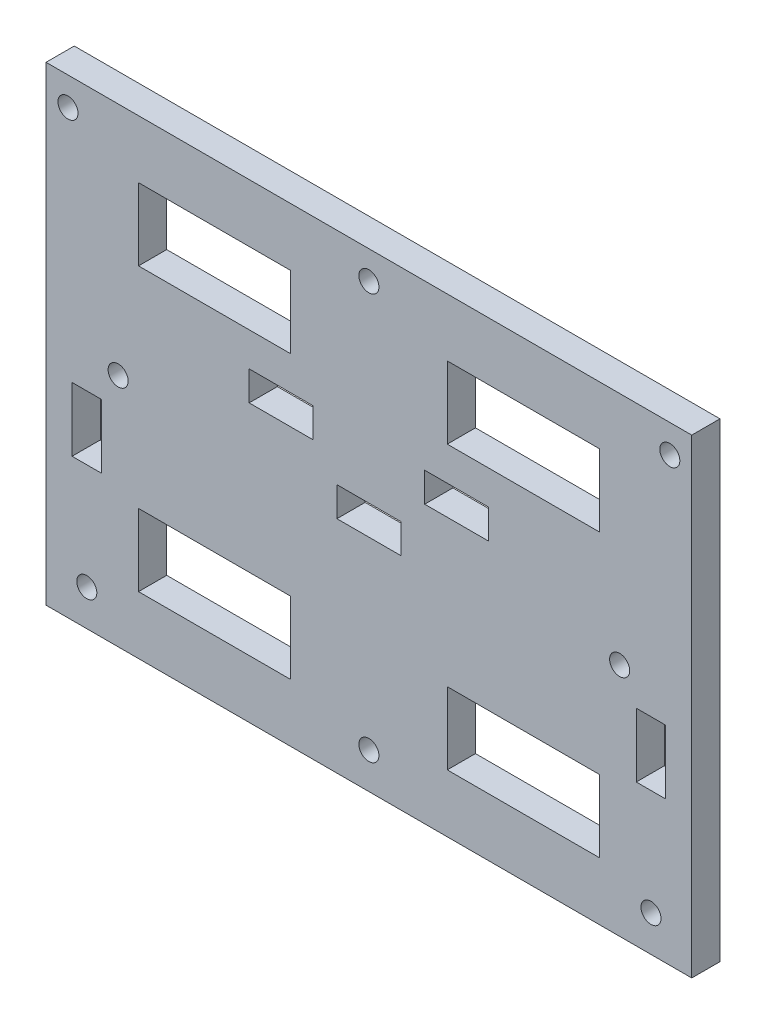
SolidWorks part; units mm, degrees
ref_plane "Front Plane" through (0, 0, 0) normal (0, 0, 1) x (1, 0, 0)
ref_plane "Top Plane" through (0, 0, 0) normal (0, 1, 0) x (1, 0, 0)
ref_plane "Right Plane" through (0, 0, 0) normal (1, 0, 0) x (0, 0, -1)
sketch "Sketch1" plane through (0, 0, 0) normal (0, 0, 1) x (1, 0, 0)
  line L0 (0, -37.5) -> (0, 37.5) construction
  line L1 (-51.5, -37.5) -> (51.5, -37.5)
  line L2 (-51.5, -37.5) -> (-51.5, 37.5)
  line L3 (-51.5, 37.5) -> (51.5, 37.5)
  line L4 (51.5, -37.5) -> (51.5, 37.5)
  line L5 (-51.5, -37.5) -> (51.5, 37.5) construction
  line L6 (-51.5, 37.5) -> (51.5, -37.5) construction
  line L7 (-51.5, 0) -> (51.5, 0) construction
  line L8 (-51.5, 22.5) -> (51.5, 22.5) construction
  line L9 (36.75, 16.75) -> (12.5, 28.25) construction
  line L10 (-36.75, 28.25) -> (-12.5, 28.25)
  line L11 (-36.75, 28.25) -> (-36.75, 16.75)
  line L12 (-36.75, 16.75) -> (-12.5, 16.75)
  line L13 (-12.5, 28.25) -> (-12.5, 16.75)
  line L14 (-36.75, 28.25) -> (-12.5, 16.75) construction
  line L15 (-36.75, 16.75) -> (-12.5, 28.25) construction
  line L16 (36.75, 28.25) -> (12.5, 16.75) construction
  line L17 (12.5, 28.25) -> (12.5, 16.75)
  line L18 (36.75, 16.75) -> (12.5, 16.75)
  line L19 (36.75, 28.25) -> (36.75, 16.75)
  line L20 (36.75, 28.25) -> (12.5, 28.25)
  line L21 (36.75, -28.25) -> (12.5, -16.75) construction
  line L22 (-36.75, -16.75) -> (-12.5, -28.25) construction
  line L23 (-36.75, -28.25) -> (-12.5, -16.75) construction
  line L24 (36.75, -16.75) -> (12.5, -28.25) construction
  line L25 (36.75, -28.25) -> (12.5, -28.25)
  line L26 (36.75, -28.25) -> (36.75, -16.75)
  line L27 (36.75, -16.75) -> (12.5, -16.75)
  line L28 (12.5, -28.25) -> (12.5, -16.75)
  line L29 (-12.5, -28.25) -> (-12.5, -16.75)
  line L30 (-36.75, -16.75) -> (-12.5, -16.75)
  line L31 (-36.75, -28.25) -> (-36.75, -16.75)
  line L32 (-36.75, -28.25) -> (-12.5, -28.25)
  point P0 (0, 0)
  point P12 (-24.625, 22.5)
  point P21 (24.625, 22.5)
  point P30 (24.625, -22.5)
  point P31 (-24.625, -22.5)
  dimension "D1" = 103
  dimension "D2" = 75
  dimension "D3" = 22.5
  dimension "D4" = 24.25
  dimension "D5" = 11.5
  dimension "D6" = 12.5
extrude "Boss-Extrude1" add sketch "Sketch1" along normal blind 4.5
sketch "Sketch2" plane through (0, 0, 4.5) normal (0, 0, 1) x (1, 0, 0)
  line L0 (0, -37.5) -> (0, 37.5) construction
  line L1 (-51.5, -37.5) -> (51.5, -37.5) construction
  line L2 (51.5, 37.5) -> (-51.5, 37.5) construction
  line L3 (-51.5, 0) -> (51.5, 0) construction
  line L4 (-51.5, 37.5) -> (-51.5, -37.5) construction
  line L5 (51.5, -37.5) -> (51.5, 37.5) construction
  line L6 (-40, 0) -> (40, 0) construction
  line L7 (-48, 33) -> (48, 33) construction
  circle A0 centre (-48, 33) radius 1.6
  circle A1 centre (48, 33) radius 1.6
  circle A2 centre (40, 0) radius 1.6
  circle A3 centre (-40, 0) radius 1.6
  circle A4 centre (0, 33) radius 1.6
  dimension "D1" = 3.2
  dimension "D7" = 3.2
  dimension "D8" = 3.2
  dimension "D9" = 3.2
  dimension "D2" = 48
  dimension "D3" = 33
  dimension "D4" = 80
  dimension "D5" = 40
  dimension "D6" = 0
extrude "screwHoles" cut sketch "Sketch2" against normal through all
sketch "Sketch3" plane through (0, 0, 4.5) normal (0, 0, 1) x (1, 0, 0)
  line L0 (-51.5, 9) -> (26.0486, 9) construction
  line L1 (-51.5, 37.5) -> (-51.5, -37.5) construction
  line L3 (0, 37.5) -> (0, -37.5) construction
  line L4 (51.5, 37.5) -> (-51.5, 37.5) construction
  line L5 (-51.5, -37.5) -> (51.5, -37.5) construction
  line L6 (19.1, 6.65) -> (8.9, 11.35) construction
  line L7 (-19.1, 11.35) -> (-8.9, 11.35)
  line L8 (-19.1, 11.35) -> (-19.1, 6.65)
  line L9 (-19.1, 6.65) -> (-8.9, 6.65)
  line L10 (-8.9, 11.35) -> (-8.9, 6.65)
  line L11 (-19.1, 11.35) -> (-8.9, 6.65) construction
  line L12 (-19.1, 6.65) -> (-8.9, 11.35) construction
  line L13 (19.1, 11.35) -> (8.9, 6.65) construction
  line L14 (8.9, 11.35) -> (8.9, 6.65)
  line L15 (19.1, 6.65) -> (8.9, 6.65)
  line L16 (19.1, 11.35) -> (19.1, 6.65)
  line L17 (19.1, 11.35) -> (8.9, 11.35)
  line L18 (-51.5, 37.5) -> (-51.5, -37.5) construction
  point P2 (-51.5, 0)
  point P12 (-14, 9)
  point P21 (14, 9)
  dimension "D1" = 10.2
  dimension "D2" = 4.7
  dimension "D3" = 14
  dimension "D4" = 9
extrude "BeltClamp" cut sketch "Sketch3" against normal through all
sketch "Sketch4" plane through (0, 0, 4.5) normal (0, 0, 1) x (1, 0, 0)
  line L0 (-51.5, 0) -> (51.5, 0) construction
  line L1 (-51.5, 37.5) -> (-51.5, -37.5) construction
  line L2 (51.5, -37.5) -> (51.5, 37.5) construction
  line L4 (-5.1, 2.35) -> (5.1, 2.35)
  line L5 (-5.1, 2.35) -> (-5.1, -2.35)
  line L6 (-5.1, -2.35) -> (5.1, -2.35)
  line L7 (5.1, 2.35) -> (5.1, -2.35)
  line L8 (-5.1, 2.35) -> (5.1, -2.35) construction
  line L9 (-5.1, -2.35) -> (5.1, 2.35) construction
  circle A0 centre (-40, 0) radius 1.6 construction
  point P6 (0, 0)
  dimension "D1" = 10.2
  dimension "D2" = 4.7
  dimension "D3" = 0
extrude "Cut-Extrude3" cut sketch "Sketch4" against normal through all
sketch "Sketch5" plane through (0, 0, 4.5) normal (0, 0, 1) x (1, 0, 0)
  line L0 (-51.5, -9.75) -> (51.5, -9.75) construction
  line L1 (-51.5, 37.5) -> (-51.5, -37.5) construction
  line L2 (51.5, -37.5) -> (51.5, 37.5) construction
  line L3 (5.1, -2.35) -> (5.1, 2.35) construction
  line L4 (0, -37.5) -> (0, 37.5) construction
  line L5 (-51.5, -37.5) -> (51.5, -37.5) construction
  line L6 (51.5, 37.5) -> (-51.5, 37.5) construction
  line L7 (-42.65, -14.85) -> (-47.35, -4.65) construction
  line L8 (42.65, -4.65) -> (47.35, -4.65)
  line L9 (42.65, -4.65) -> (42.65, -14.85)
  line L10 (42.65, -14.85) -> (47.35, -14.85)
  line L11 (47.35, -4.65) -> (47.35, -14.85)
  line L12 (42.65, -4.65) -> (47.35, -14.85) construction
  line L13 (42.65, -14.85) -> (47.35, -4.65) construction
  line L14 (-42.65, -4.65) -> (-47.35, -14.85) construction
  line L15 (-47.35, -4.65) -> (-47.35, -14.85)
  line L16 (-42.65, -14.85) -> (-47.35, -14.85)
  line L17 (-42.65, -4.65) -> (-42.65, -14.85)
  line L18 (-42.65, -4.65) -> (-47.35, -4.65)
  line L19 (45, -9.75) -> (45, -37.5) construction
  line L20 (-45, -9.75) -> (-45, -37.5) construction
  line L21 (-45, -31.75) -> (45, -31.75) construction
  circle A0 centre (45, -31.75) radius 1.6
  circle A1 centre (-45, -31.75) radius 1.6
  circle A2 centre (0, -31.75) radius 1.6
  point P6 (5.1, 0)
  point P15 (45, -9.75)
  point P24 (-45, -9.75)
  dimension "D5" = 3.2
  dimension "D7" = 3.2
  dimension "D1" = 9.75
  dimension "D2" = 10.2
  dimension "D3" = 4.7
  dimension "D4" = 45
  dimension "D6" = 22
extrude "Cut-Extrude4" cut sketch "Sketch5" against normal through all
sketch "Sketch6" plane through (0, 0, 4.5) normal (0, 0, 1) x (1, 0, 0)
  line L0 (-47.35, -9.75) -> (47.35, -9.75) construction
  line L1 (-47.35, -4.65) -> (-47.35, -14.85) construction
  line L2 (47.35, -14.85) -> (47.35, -4.65) construction
  line L3 (0, -2.35) -> (0, -37.5) construction
  line L4 (-5.1, -2.35) -> (5.1, -2.35) construction
  line L5 (-51.5, -37.5) -> (51.5, -37.5) construction
  line L6 (45, -14.85) -> (45, -4.65) construction
  line L7 (42.65, -14.85) -> (47.35, -14.85) construction
  line L8 (47.35, -4.65) -> (42.65, -4.65) construction
  line L9 (42.65, -4.65) -> (42.65, -14.85) construction
  line L10 (41.65, -15.85) -> (48.35, -15.85)
  line L11 (41.65, -15.85) -> (41.65, -3.65)
  line L12 (41.65, -3.65) -> (48.35, -3.65)
  line L13 (48.35, -15.85) -> (48.35, -3.65)
  line L14 (41.65, -15.85) -> (48.35, -3.65) construction
  line L15 (41.65, -3.65) -> (48.35, -15.85) construction
  line L16 (-41.65, -3.65) -> (-48.35, -15.85) construction
  line L17 (-41.65, -15.85) -> (-48.35, -3.65) construction
  line L18 (-45, -14.85) -> (-45, -4.65) construction
  line L19 (-48.35, -15.85) -> (-48.35, -3.65)
  line L20 (-41.65, -3.65) -> (-48.35, -3.65)
  line L21 (-41.65, -15.85) -> (-41.65, -3.65)
  line L22 (-41.65, -15.85) -> (-48.35, -15.85)
  circle A0 centre (45, -9.75) radius 1.6
  circle A1 centre (-45, -9.75) radius 1.6
  point P18 (45, -9.75)
  dimension "D3" = 3.2
  dimension "D1" = 1
  dimension "D2" = 1
extrude "FrontToRear1" [suppressed] add sketch "Sketch6" against normal up to surface (4.5 mm away) up to face at (1.6, -31.75, 0)
sketch "Sketch7" plane through (0, 0, 4.5) normal (0, 0, 1) x (1, 0, 0)
  line L0 (5.1, 2.35) -> (-5.1, 2.35) construction
  line L1 (-45, -3.35) -> (45, -3.35)
  line L2 (-45, -3.35) -> (-45, 3.35)
  line L3 (-45, 3.35) -> (45, 3.35)
  line L4 (45, -3.35) -> (45, 3.35)
  line L5 (-45, -3.35) -> (45, 3.35) construction
  line L6 (-45, 3.35) -> (45, -3.35) construction
  circle A0 centre (40, 0) radius 1.6 construction
  point P0 (0, 0)
  dimension "D1" = 1
  dimension "D2" = 5
extrude "FrontToRear2" [suppressed] add sketch "Sketch7" against normal through all
equation "\"X-ROD-SPACING\"=45"
equation "\"Y-ROD-SPACING\"=75"
equation "\"Z-ROD-SPACING\"=17.5"
equation "\"Y-BED-OFFSET\"=2"
equation "\"Y-BED-ROD-INSET\"=3.5"
equation "\"Y-BED-SCREW-SPACING\"=209"
equation "\"Y-BED-SCREW-CUTOUT-SLOT-HEIGHT\"=1"
equation "\"T-SLOT-NUT-FILLET-RADIUS\"=0.25"
equation "\"T-SLOT-SCREW-SHAFT-RADIUS\"=1.75"
equation "\"T-SLOT-SCREW-SHAFT-CUTOUT-LENGTH\"=10.5"
equation "\"T-SLOT-NUT-DEPTH\"=4.2"
equation "\"T-SLOT-NUT-WIDTH\"=3"
equation "\"T-SLOT-NUT-END-DISTANCE\"=8"
equation "\"ACRYLIC-THICKNESS\"=10"
equation "\"ACRYLIC-THICKNESS2\"=4.5"
equation "\"ACRYLIC-TAB-CUTOUT-SIZE\"=\"ACRYLIC-THICKNESS\"+\"ACRYLIC-TAB-TOLERANCE\"*2"
equation "\"ACRYLIC-TAB-WIDTH\"=\"ACRYLIC-THICKNESS\""
equation "\"ACRYLIC-M3-HOLE\"=3.2"
equation "\"SMOOTHROD-CAP-SCREW-DISTANCE\"=20"
equation "\"FRAME-WIDTH-INNER\"=370"
equation "\"NEMA17-HOLE-SPACING\"=31"
equation "\"NEMA17-CENTRAL-CUTOUT\"=22.5"
equation "\"Z-BRACKET-REACH\"=55"
equation "\"Z-ROD-INSET\"=16"
equation "\"TOP-BRACKET-SPACING\"=40"
equation "\"SMOOTHROD-X-LENGTH\"=350"
equation "\"SMOOTHROD-Y-LENGTH\"=350"
equation "\"SMOOTHROD-Z-LENGTH\"=350"
equation "\"SMOOTHROD-TIGHTENING-HEADROOM\"=1"
equation "\"LEADSCREW-Z-LENGTH\"=300"
equation "\"SCREW-LENGTH-FRAME\"=\"ACRYLIC-THICKNESS\" + 10"
equation "\"SCREW-LENGTH-MOTOR\"=\"ACRYLIC-THICKNESS\" + 5"
equation "\"SCREW-HEAD-RADIUS\"=6"
equation "\"PRINTED-X-SMOOTHROD-DIAMETER\"=8.2"
equation "\"PRINTED-X-SMOOTHROD-CUTOUT\"=10"
equation "\"PRINTED-X-BASE-HEIGHT\"=10"
equation "\"PRINTED-LM8UU-CUTOUT-SIZE\"=15.25"
equation "\"PRINTED-LM8UU-CUTOUT-LENGTH\"=24.5"
equation "\"PRINTED-X-IDLER-HEIGHT\"=16"
equation "\"PSU-MOUNTING-WIDTH\"=95"
equation "\"PSU-MOUNTING-HEIGHT\"=177"
equation "\"Y-BELT-TO-ROD-DISTANCE\"=20"
equation "\"SPOOL-HOLDER-ROD-SPACING\"=150"
equation "\"D3@Sketch1\"=\"X-ROD-SPACING\"/2"
equation "\"D4@Sketch1\"=\"ACRYLIC-X-CARRIAGE-LM8UU-CUTOUT-WIDTH\""
equation "\"D1@Boss-Extrude1\"=\"ACRYLIC-THICKNESS2\""
equation "\"D1@Sketch2\"=\"ACRYLIC-M3-HOLE\""
equation "\"D1@Sketch3\"=\"ACRYLIC-TAB-CUTOUT-SIZE\""
equation "\"D2@Sketch3\"=\"ACRYLIC-THICKNESS2\"+\"ACRYLIC-TAB-TOLERANCE\"*2"
equation "\"ACRYLIC-X-CARRIAGE-WIDTH\"=55"
equation "\"ACRYLIC-X-CARRIAGE-HEIGHT\"=75"
equation "\"D2@Sketch1\"=\"ACRYLIC-X-CARRIAGE-HEIGHT\""
equation "\"ACRYLIC-X-CARRIAGE-CENTER-TAB-SPACING\"=14"
equation "\"D3@Sketch3\"=\"ACRYLIC-X-CARRIAGE-CENTER-TAB-SPACING\""
equation "\"SCREW-LENGTH-EXTRUDER\"=28"
equation "\"ACRYLIC-X-CARRIAGE-SCREW-SPACING-X\"=15"
equation "\"ACRYLIC-X-CARRIAGE-SCREW-SPACING-Y\"=33"
equation "\"D3@Sketch2\"=\"ACRYLIC-X-CARRIAGE-SCREW-SPACING-Y\""
equation "\"D1@Sketch4\"=\"ACRYLIC-TAB-CUTOUT-SIZE\""
equation "\"D2@Sketch4\"=\"ACRYLIC-THICKNESS2\"+\"ACRYLIC-TAB-TOLERANCE\"*2"
equation "\"D2@Sketch5\"=\"ACRYLIC-TAB-CUTOUT-SIZE\""
equation "\"D3@Sketch5\"=\"ACRYLIC-THICKNESS2\"+\"ACRYLIC-TAB-TOLERANCE\"*2"
equation "\"ACRYLIC-X-CARRIAGE-EXTRUDER-SHELF-DEPTH\"=\"ACRYLIC-X-CARRIAGE-EXTRUDER-OFFSET\" + 30"
equation "\"ACRYLIC-X-CARRIAGE-EXTRUDER-BRACE-SPACING\"=23"
equation "\"D4@Sketch5\"=\"ACRYLIC-X-CARRIAGE-DUAL-MOUNT-BRACE-WIDTH\""
equation "\"D1@Sketch5\"=\"ACRYLIC-THICKNESS2\"/2 + 7.5"
equation "\"D4@Sketch2\"=\"ACRYLIC-X-CARRIAGE-DUAL-MOUNT-SCREW-WIDTH\"*2"
equation "\"D5@Sketch2\"=\"ACRYLIC-X-CARRIAGE-DUAL-MOUNT-SCREW-WIDTH\""
equation "\"D7@Sketch2\"=\"ACRYLIC-M3-HOLE\""
equation "\"D8@Sketch2\"=\"ACRYLIC-M3-HOLE\""
equation "\"ACRYLIC-X-CARRIAGE-LM8UU-CUTOUT-WIDTH\"=24.25"
equation "\"ACRYLIC-TAB-TOLERANCE\"=.1"
equation "\"ACRYLIC-X-CARRIAGE-EXTRUDER-OFFSET\"=26"
equation "\"ACRYLIC-X-CARRIAGE-EXTRUDER-ANGLE\"=90"
equation "\"ACRYLIC-X-CARRIAGE-EXTRUDER-BRACE-TAB-OFFSET\"=20"
equation "\"ACRYLIC-X-CARRIAGE-EXTRUDER-BRACE-HEIGHT\"=35"
equation "\"ACRYLIC-X-CARRIAGE-EXTRUDER-BRACE-SCREW-SPACING\"=22"
equation "\"D5@Sketch5\"=\"ACRYLIC-M3-HOLE\""
equation "\"D3@Sketch6\"=\"ACRYLIC-M3-HOLE\""
equation "\"ACRYLIC-X-CARRIAGE-DUAL-WIDTH-MULTIPLIER\"=1.65"
equation "\"ACRYLIC-X-CARRIAGE-DUAL-HOTEND-SPACING\"=42"
equation "\"ACRYLIC-X-CARRIAGE-DUAL-WIDTH\"=103"
equation "\"ACRYLIC-X-CARRIAGE-DUAL-HOTEND-SEPARATION\"=35"
equation "\"ACRYLIC-X-CARRIAGE-DUAL-MOUNT-PLATE-DEPTH\"=76"
equation "\"ACRYLIC-X-CARRIAGE-DUAL-MOUNT-BRACE-WIDTH\"=45"
equation "\"ACRYLIC-X-CARRIAGE-DUAL-MOUNT-SCREW-WIDTH\"=40"
equation "\"D1@Sketch1\"=\"ACRYLIC-X-CARRIAGE-DUAL-WIDTH\""
equation "\"D9@Sketch2\"=\"ACRYLIC-M3-HOLE\""
equation "\"D7@Sketch5\"=\"ACRYLIC-M3-HOLE\""
equation "\"ACRYLIC-X-CARRIAGE-LM8UU-CUTOUT-HEIGHT\"=11.5"
equation "\"D5@Sketch1\"=\"ACRYLIC-X-CARRIAGE-LM8UU-CUTOUT-HEIGHT\""
